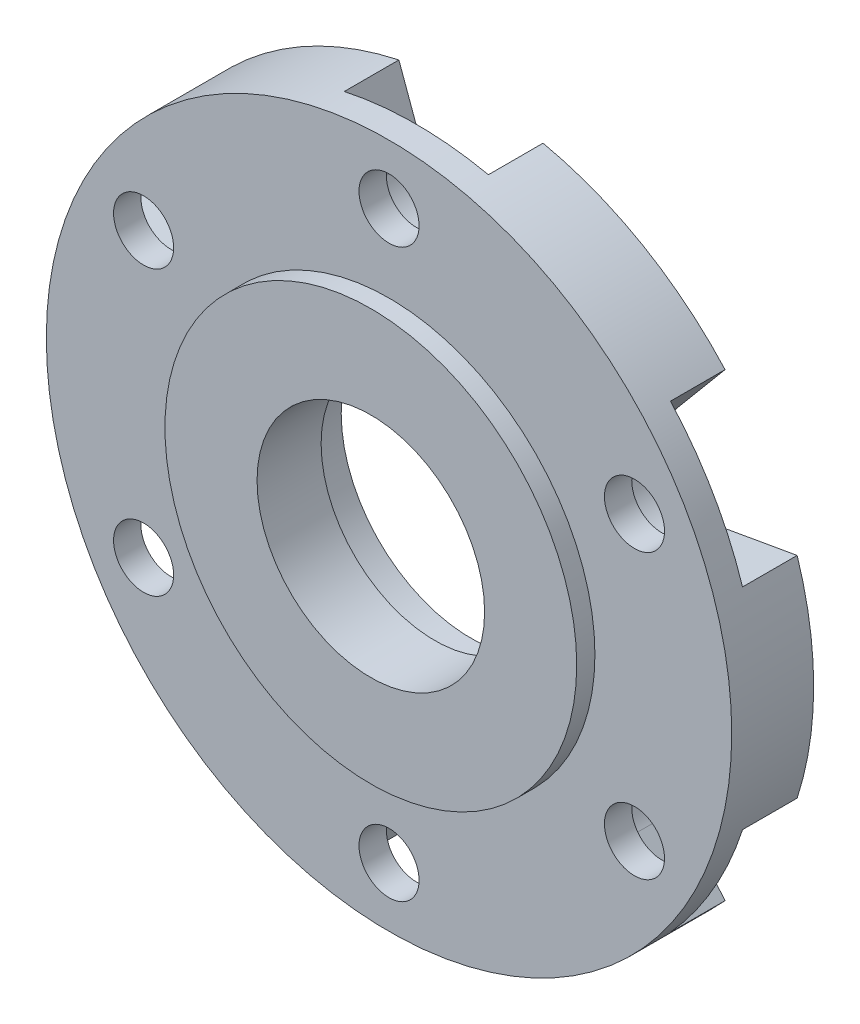
SolidWorks part; units mm, degrees
material "6061-T6 (SS)"
ref_plane "Front Plane" through (0, 0, 0) normal (0, 0, 1) x (1, 0, 0)
ref_plane "Top Plane" through (0, 0, 0) normal (0, 1, 0) x (1, 0, 0)
ref_plane "Right Plane" through (0, 0, 0) normal (1, 0, 0) x (0, 0, -1)
sketch "Sketch Spindle Skeleton" plane through (0, 0, 0) normal (1, 0, 0) x (0, 0, -1)
  line L0 (-95.847, -9.5) -> (-164, -9.5)
  line L5 (-1000, 0) -> (49000, 0)
  line L6 (0, -9.5) -> (0, 9.5)
  line L13 (0, 9.5) -> (-45.847, 9.5)
  line L26 (-45.847, 9.5) -> (-45.847, 14)
  line L27 (-45.847, 14) -> (-95.847, 14)
  line L32 (-95.847, 14) -> (-95.847, 9.5)
  line L34 (-180, 7) -> (-180, -7)
  line L36 (-95.847, -9.5) -> (-95.847, -14)
  line L37 (-95.847, -14) -> (-45.847, -14)
  line L38 (-45.847, -14) -> (-45.847, -9.5)
  line L39 (0, -9.5) -> (-45.847, -9.5)
  line L40 (-25.305, 37.6491) -> (-16.305, 37.6491)
  line L41 (-111.341, 22.6187) -> (-95.847, 22.6187)
  line L42 (-111.341, 22.6187) -> (-111.341, -22.6187)
  line L43 (-111.341, -22.6187) -> (-95.847, -22.6187)
  line L44 (-95.847, 22.6187) -> (-95.847, -22.6187)
  line L45 (-111.341, 22.6187) -> (-95.847, -22.6187) construction
  line L46 (-111.341, -22.6187) -> (-95.847, 22.6187) construction
  line L47 (-30.353, 22.6187) -> (-45.847, 22.6187)
  line L48 (-30.353, 22.6187) -> (-30.353, -22.6187)
  line L49 (-30.353, -22.6187) -> (-45.847, -22.6187)
  line L50 (-45.847, 22.6187) -> (-45.847, -22.6187)
  line L51 (-30.353, 22.6187) -> (-45.847, -22.6187) construction
  line L52 (-30.353, -22.6187) -> (-45.847, 22.6187) construction
  line L59 (-16.305, 37.6491) -> (-16.305, -37.6491)
  line L60 (-16.305, -37.6491) -> (-25.305, -37.6491)
  line L61 (-25.305, -22.6187) -> (-27.305, -22.6187)
  line L62 (-27.305, -22.6187) -> (-27.305, -12.5)
  line L63 (-27.305, -12.5) -> (-25.305, -12.5)
  line L64 (-25.305, -12.5) -> (-25.305, 12.5)
  line L65 (-25.305, 12.5) -> (-27.305, 12.5)
  line L66 (-27.305, 12.5) -> (-27.305, 22.6187)
  line L67 (-27.305, 22.6187) -> (-25.305, 22.6187)
  line L68 (-25.305, 22.6187) -> (-25.305, 37.6491)
  line L69 (-25.305, -22.6187) -> (-25.305, -37.6491)
  line L71 (-119.469, 37.6491) -> (-26.305, 37.6491)
  line L72 (-119.469, 37.6491) -> (-119.469, -37.6491)
  line L73 (-119.469, -37.6491) -> (-26.305, -37.6491)
  line L74 (-26.305, 37.6491) -> (-26.305, -37.6491)
  line L75 (-119.469, 37.6491) -> (-26.305, -37.6491) construction
  line L76 (-119.469, -37.6491) -> (-26.305, 37.6491) construction
  line L77 (-164, -9.5) -> (-164, -7)
  line L78 (-164, -7) -> (-180, -7)
  line L79 (-95.847, 9.5) -> (-164, 9.5)
  line L80 (-164, 7) -> (-180, 7)
  line L81 (-164, 9.5) -> (-164, 7)
  line L82 (-129.9235, 9.5) -> (-129.9235, -9.5) construction
  line L83 (-22.9235, 9.5) -> (-22.9235, -9.5) construction
  line L96 (-119.469, 37.6491) -> (-128.469, 37.6491)
  line L98 (-119.469, -37.6491) -> (-128.469, -37.6491)
  line L99 (-128.469, 37.6491) -> (-128.469, -37.6491)
  line L110 (-119.469, 37.6491) -> (-119.469, -37.6491)
  point P3 (0, 0)
  point P18 (-103.594, 0)
  point P24 (-38.1, 0)
  point P29 (-72.887, 0)
  point P48 (-16.305, 31.1339)
  point P70 (-128.469, 31.1339)
revolve "Main Revolve" add sketch "Sketch Spindle Skeleton" angle 360 about L5 region at (0, 23.3435, 20.997) region at (0, 17.5594, 26.805)
sketch "Sketch Center Cut" plane through (0, 0, 25.305) normal (0, 0, 1) x (1, 0, 0)
  circle A3 centre (0, 0) radius 12.5
  dimension "D1" = 25
extrude "Cut Center" cut sketch "Sketch Center Cut" against normal through all both and the other way through all
hole_wizard "CBORE for M6 SHCS1" positions "Hole wizard sketch 1" profile "Hole wizard sketch 2" counterbore size "M6" standard "ANSI Metric" end condition through all
sketch "Hole wizard sketch 1" plane through (0, 0, 16.305) normal (0, 0, -1) x (-1, 0, 0)
  point P0 (0, 31.1339)
sketch "Hole wizard sketch 2" plane through (0, 31.1339, 16.305) normal (1, 0, 0) x (0, 1, 0)
  line L0 (0, 0) -> (0, 11)
  line L1 (0, 11) -> (3.3, 11)
  line L3 (3.3, 11) -> (3.3, 6)
  line L4 (3.3, 6) -> (5.5, 6)
  line L5 (5.5, 6) -> (5.5, 0)
  line L7 (5.5, 0) -> (0, 0)
  line L11 (0, -6.35) -> (0, 107.95) construction
  dimension "Thru Hole Dia." = 6.6
  dimension "Thru Hole Depth" = 11
  dimension "C'Bore Dia." = 11
  dimension "C'Bore Depth" = 6
pattern_circular "CirPattern1" count 6 over 360 about axis through (0, 0, 16.305) along (0, 0, 1) of "CBORE for M6 SHCS1"
sketch "Sketch1" plane through (0, 0, 16.305) normal (0, 0, -1) x (-1, 0, 0)
  circle A0 centre (0, 0) radius 14.2558
  dimension "D1" = 28.5115
extrude "Cut-Extrude1" cut sketch "Sketch1" against normal blind 3.9624
sketch "Sketch2" plane through (0, 0, 16.305) normal (0, 0, -1) x (-1, 0, 0)
  line L0 (-5.1683, 29.2528) -> (-7.9179, 36.8071)
  line L1 (0, 31.1339) -> (0, 37.65) construction
  line L2 (5.1683, 29.2528) -> (7.9179, 36.8071)
  circle A0 centre (0, 31.1339) radius 5.5 construction
  circle A1 centre (0, 0) radius 37.6491 construction
  arc A2 (-5.1683, 29.2528) -> (5.1683, 29.2528) centre (0, 31.1339) ccw
  point P37 (0.065, 0.0375)
  circle M8 centre (0, 31.1339) radius 5.5
  circle M9 centre (0, 0) radius 37.6491
  dimension "D1" = 20
extrude "Cut-Extrude2" cut sketch "Sketch2" against normal up to surface (6 mm away) contours L1 L2 M8 M9 | L1 L0 M8 M9 region at (4.7304, 35.5149, 16.305) region at (-4.7304, 35.5149, 16.305) up to face at (23.6628, -15.567, 22.305)
pattern_circular "CirPattern2" count 6 over 360 about axis through (0, 0, 1000) along (0, 0, 1) of "Cut-Extrude2" reverse direction yes
